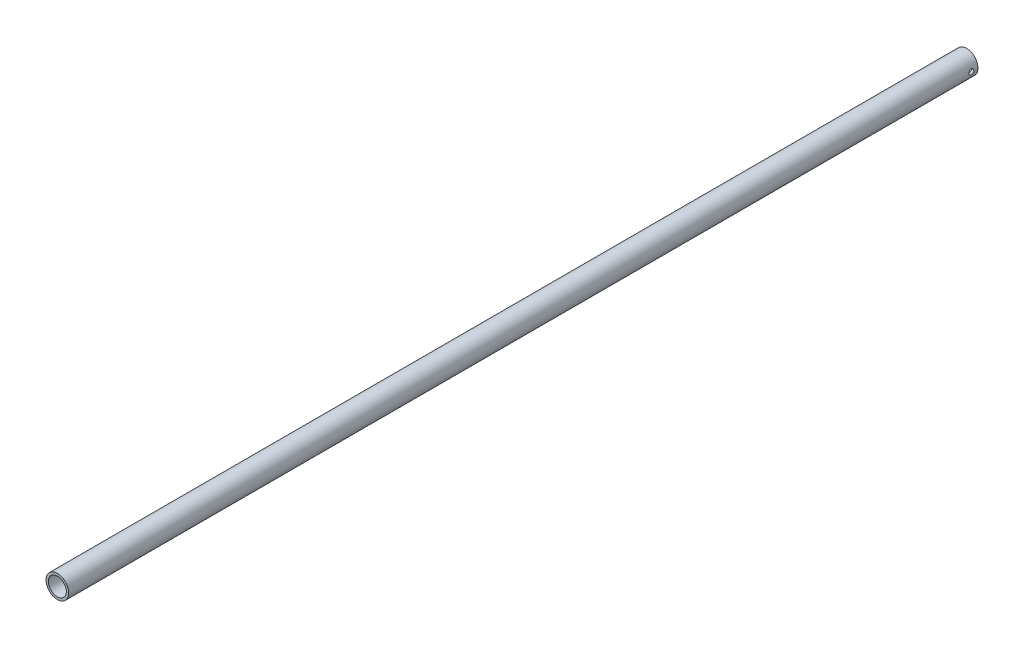
SolidWorks part; units mm, degrees
material "6061-T6 (SS)"
ref_plane "Front" through (0, 0, 0) normal (0, 0, 1) x (1, 0, 0)
ref_plane "Top" through (0, 0, 0) normal (0, 1, 0) x (1, 0, 0)
ref_plane "Right" through (0, 0, 0) normal (1, 0, 0) x (0, 0, -1)
sketch "Sketch1" plane through (0, 0, 0) normal (0, 0, 1) x (1, 0, 0)
  circle A0 centre (0, 0) radius 15.24
  circle A1 centre (0, 0) radius 12.065
  dimension "D1" = 3.175
  dimension "D2" = 30.48
extrude "Boss-Extrude1" add sketch "Sketch1" along normal blind 1219.2
ref_plane "Plane1" through (0, -15.24, 0) normal (0, -1, 0) x (-1, 0, 0)
sketch "Sketch2" plane through (0, -15.24, 0) normal (0, 1, 0) x (1, 0, 0)
  line L0 (0, 0) -> (0, -180.975) construction
  line L1 (0, -180.975) -> (0, -1117.6) construction
  line L2 (0, -1117.6) -> (0, -1193.8) construction
  line L3 (-15.24, -1219.2) -> (15.24, -1219.2) construction
  point P3 (0, -88.9)
  point P8 (0, -282.575)
  point P9 (0, -6.35)
  dimension "D1" = 180.975
  dimension "D2" = 88.9
  dimension "D3" = 76.2
  dimension "D4" = 25.4
  dimension "D5" = 101.6
  dimension "D6" = 6.35
ref_plane "Plane2" through (-15.24, 0, 0) normal (-1, 0, 0) x (0, 0, 1)
sketch "Sketch9" plane through (-15.24, 0, 0) normal (-1, 0, 0) x (0, 0, 1)
  line L0 (0, 0) -> (88.9, 0) construction
  line L1 (88.9, 0) -> (282.575, 0) construction
  point P3 (8.89, 0)
  dimension "D1" = 88.9
  dimension "D2" = 193.675
  dimension "D3" = 8.89
hole_wizard "1/4 Clearance Hole3" positions "Sketch11" profile "Sketch10" hole size "1/4" standard "ANSI Inch" end condition through all
sketch "Sketch11" plane through (-15.24, 0, 0) normal (-1, 0, 0) x (0, 0, 1)
  point P7 (8.89, 0)
sketch "Sketch10" plane through (-15.24, 0, 8.89) normal (0, 1, 0) x (0, 0, 1)
  line L0 (0, 0) -> (0, 30.48)
  line L1 (0, 30.48) -> (3.3782, 30.48)
  line L2 (3.3782, 30.48) -> (3.3782, 0)
  line L5 (3.3782, 0) -> (0, 0)
  line L11 (0, -6.35) -> (0, 107.95) construction
  dimension "Thru Hole Dia." = 6.7564
  dimension "Thru Hole Depth" = 30.48
